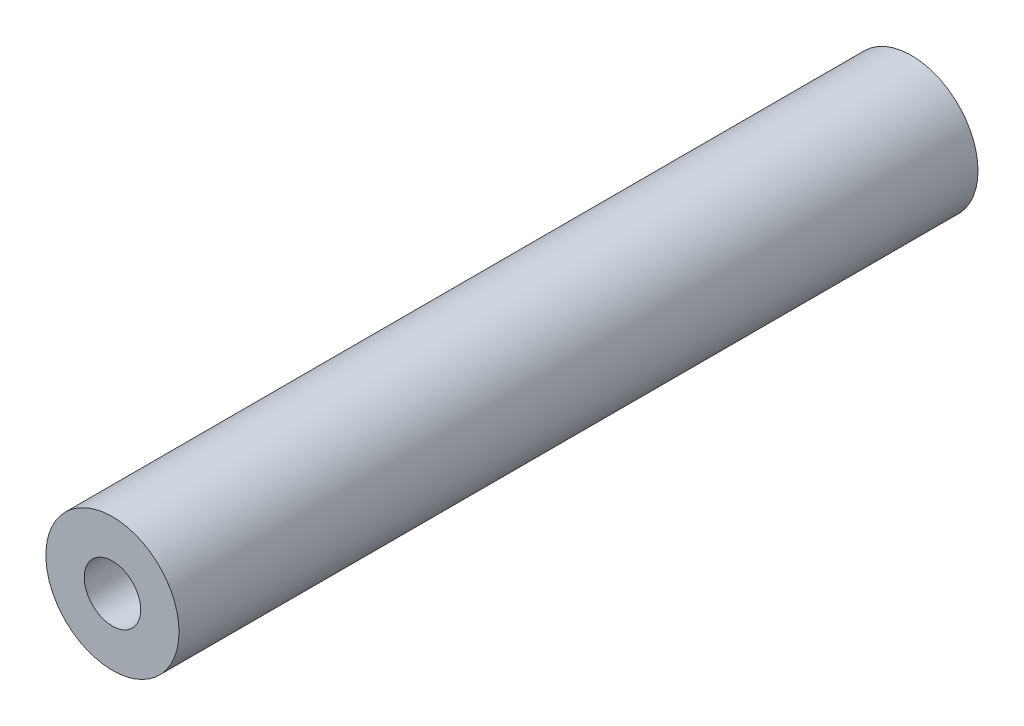
SolidWorks part; units mm, degrees
ref_plane "Front Plane" through (0, 0, 0) normal (0, 0, 1) x (1, 0, 0)
ref_plane "Top Plane" through (0, 0, 0) normal (0, 1, 0) x (1, 0, 0)
ref_plane "Right Plane" through (0, 0, 0) normal (1, 0, 0) x (0, 0, -1)
sketch "Sketch1" plane through (0, 0, 0) normal (0, 0, 1) x (1, 0, 0)
  circle A1 centre (0, 0) radius 4.7625
  dimension "D1" = 9.525
extrude "Boss-Extrude1" add sketch "Sketch1" along normal blind 57.15
hole_wizard "#10-32 Tapped Hole1" positions "3DSketch1" profile "Sketch2" tap size "#10-32" standard "ANSI Inch" end condition through all
sketch3d "3DSketch1"
  line L0 (0, 0, 57.15) -> (0, 0, 0) construction
  point P0 (0, 0, 57.15)
  point P4 (0, 0, 0)
sketch "Sketch2" plane through (0, 0, 57.15) normal (1, 0, 0) x (0, -1, 0)
  line L0 (0, 0) -> (0, 57.15)
  line L1 (0, 57.15) -> (2.0193, 57.15)
  line L2 (2.0193, 57.15) -> (2.0193, 0)
  line L5 (2.0193, 0) -> (0, 0)
  line L11 (0, -6.35) -> (0, 107.95) construction
  dimension "Thru Tap Drill Dia." = 4.0386
  dimension "Thru Tap Drill Depth" = 57.15
cosmetic thread "Hole Thread1" parameters "D2"=4.826
cosmetic thread "Hole Thread2" parameters "D2"=4.826
